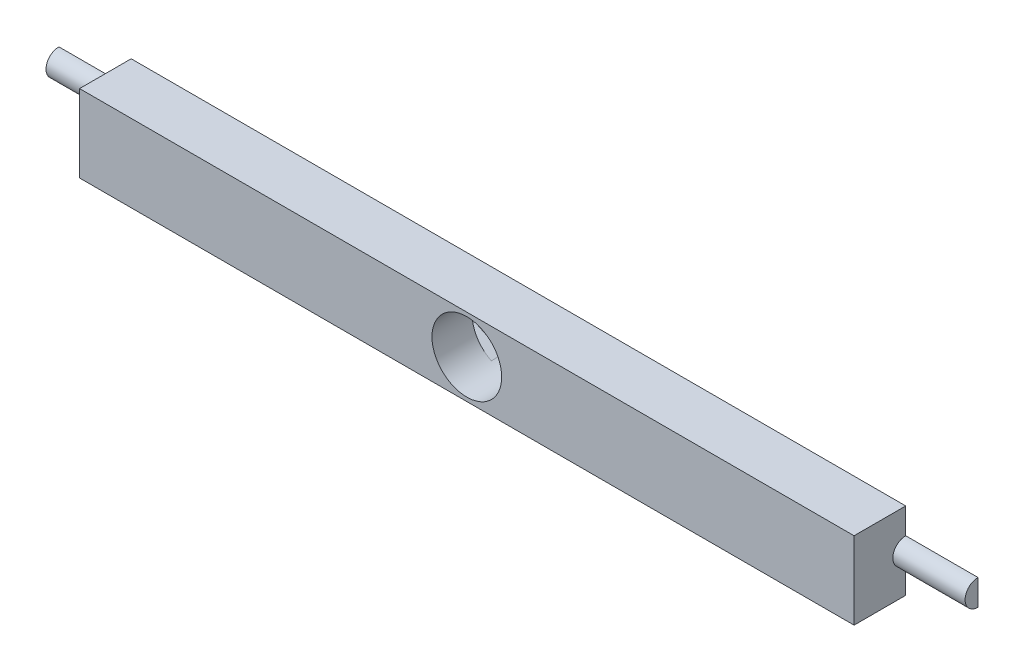
SolidWorks part; units mm, degrees
ref_plane "前视基准面" through (0, 0, 0) normal (0, 0, 1) x (1, 0, 0)
ref_plane "上视基准面" through (0, 0, 0) normal (0, 1, 0) x (1, 0, 0)
ref_plane "右视基准面" through (0, 0, 0) normal (1, 0, 0) x (0, 0, -1)
other "Configuration Table"
sketch "草图1" plane through (0, 0, 0) normal (0, 0, 1) x (1, 0, 0)
  line L0 (0, 0) -> (79.8665, 0) construction
  line L1 (0, 0) -> (0, 25.0088) construction
  line L2 (-150, 0) -> (-150, 30)
  line L3 (-150, 30) -> (150, 30)
  line L4 (150, 30) -> (150, 0)
  line L5 (150, 0) -> (-150, 0)
  point P7 (0, 30)
  dimension "D1" = 300
  dimension "D2" = 30
extrude "凸台-拉伸1" add sketch "草图1" along normal blind 20 contours L2 L3 L4 L5
sketch "草图2" plane through (-150, 0, 0) normal (-1, 0, 0) x (0, 0, 1)
  line L0 (0, 0) -> (0, 30) construction
  line L1 (0, 0) -> (0, 30) construction
  line L3 (0, 15) -> (20, 15) construction
  line L6 (0, 20) -> (0, 10)
  arc A0 (0, 10) -> (0, 20) centre (0, 15) ccw
  dimension "D1" = 5
extrude "凸台-拉伸2" add sketch "草图2" along normal blind 28 and the other way blind 328 contours L6 A0
sketch "草图3" plane through (0, 0, 0) normal (0, 0, -1) x (-1, 0, 0)
  line L0 (0, 0) -> (0, 129.1579) construction
  line L1 (-178, 15) -> (178, 15) construction
  line L2 (-6.0203, 27.0833) -> (-20.8412, 19.6991)
  line L3 (6.0203, 27.0833) -> (20.8412, 19.6991)
  line L4 (6.0203, 2.9167) -> (20.8412, 10.3009)
  line L5 (-6.0203, 2.9167) -> (-20.8412, 10.3009)
  circle A0 centre (0, 15) radius 4
  circle A1 centre (0, 15) radius 6
  circle A2 centre (0, 15) radius 13.25
  circle A3 centre (18.5, 15) radius 2.4
  circle A4 centre (0, 15) radius 13.5
  circle A5 centre (-18.5, 15) radius 2.4
  arc A6 (-20.8412, 19.6991) -> (-20.8412, 10.3009) centre (-18.5, 15) ccw
  arc A7 (20.8412, 19.6991) -> (20.8412, 10.3009) centre (18.5, 15) cw
  point P20 (-23.75, 15)
  dimension "D1" = 8
  dimension "D2" = 2
  dimension "D4" = 4.8
  dimension "D6" = 0.25
  dimension "D7" = 10.5
  dimension "D5" = 18.5
  dimension "D3" = 7.25
extrude "切除-拉伸1" cut sketch "草图3" against normal through all contours A0 region at (0, 15, 0)
extrude "切除-拉伸2" cut sketch "草图3<3>" against normal through all contours A1 A0 region at (5.8303, 15, 0)
sketch "草图3<3>" plane through (0, 0, 0) normal (0, 0, -1) x (-1, 0, 0) same geometry as "草图3"
extrude "切除-拉伸3" cut sketch "草图3<4>" against normal through all contours A2 A1 | A4 A2 region at (0, 28.4618, 0) region at (12.8752, 15, 0)
sketch "草图3<4>" plane through (0, 0, 0) normal (0, 0, -1) x (-1, 0, 0) same geometry as "草图3"
extrude "切除-拉伸4" cut sketch "草图3<5>" against normal blind 4.5 contours L2 A6 L5 A4 A5 | A7 L3 A4 L4 A3 region at (13.7997, 15, 0) region at (-13.2971, 23.1229, 0)
sketch "草图3<5>" plane through (0, 0, 0) normal (0, 0, -1) x (-1, 0, 0) same geometry as "草图3"
extrude "切除-拉伸5" cut sketch "草图3<6>" against normal blind 5 contours A5 | A3 region at (-18.5, 15, 0) region at (18.5, 15, 0)
sketch "草图3<6>" plane through (0, 0, 0) normal (0, 0, -1) x (-1, 0, 0) same geometry as "草图3"
